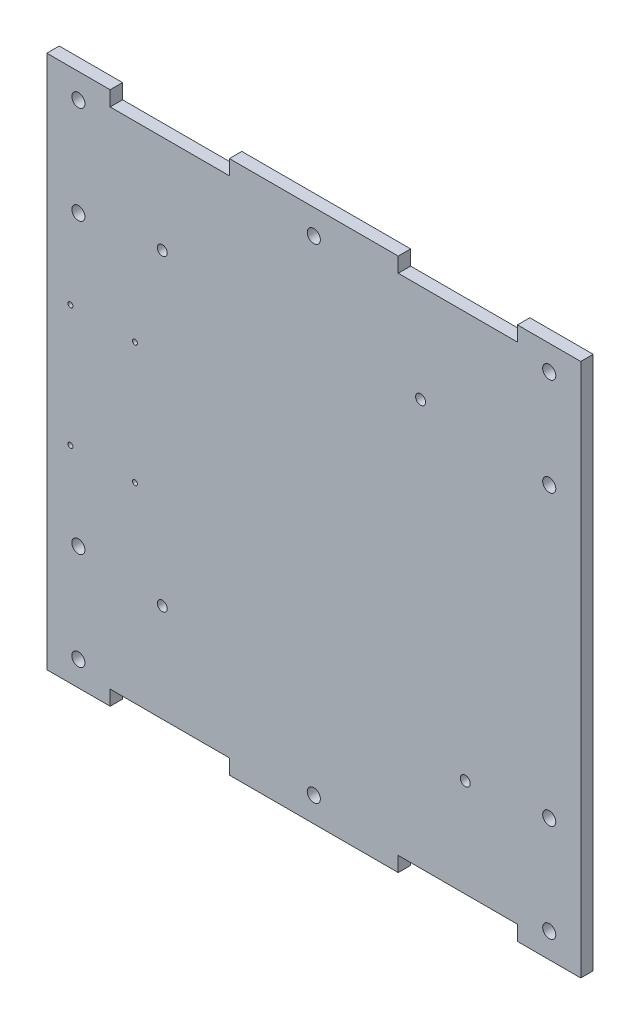
SolidWorks part; units mm, degrees
material "ABS PC"
ref_plane "Front Plane" through (0, 0, 0) normal (0, 0, 1) x (1, 0, 0)
ref_plane "Top Plane" through (0, 0, 0) normal (0, 1, 0) x (1, 0, 0)
ref_plane "Right Plane" through (0, 0, 0) normal (1, 0, 0) x (0, 0, -1)
sketch "Sketch2" plane through (0, 0, 0) normal (0, 0, 1) x (1, 0, 0)
  line L0 (-148.1492, 0) -> (167.2874, 0) construction
  line L1 (-136.525, -136.525) -> (136.525, -136.525)
  line L2 (-136.525, -136.525) -> (-136.525, 136.525)
  line L3 (-136.525, 136.525) -> (136.525, 136.525)
  line L4 (136.525, -136.525) -> (136.525, 136.525)
  line L5 (-136.525, -136.525) -> (136.525, 136.525) construction
  line L6 (-136.525, 136.525) -> (136.525, -136.525) construction
  line L7 (0, 204.6077) -> (0, -224.7364) construction
  circle A0 centre (-120.396, 123.825) radius 3.35
  circle A1 centre (-120.396, 73.787) radius 3.35
  circle A2 centre (0, 123.825) radius 3.35
  circle A3 centre (120.396, 73.787) radius 3.35
  circle A4 centre (120.396, 123.825) radius 3.35
  circle A5 centre (120.396, -123.825) radius 3.35
  circle A6 centre (120.396, -73.787) radius 3.35
  circle A7 centre (0, -123.825) radius 3.35
  circle A8 centre (-120.396, -73.787) radius 3.35
  circle A9 centre (-120.396, -123.825) radius 3.35
  point P0 (0, 0)
  dimension "D4" = 6.7
  dimension "D7" = 6.7
  dimension "D8" = 6.7
  dimension "D1" = 273.05
  dimension "D2" = 273.05
  dimension "D3" = 120.396
  dimension "D5" = 123.825
  dimension "D6" = 50.038
extrude "Boss-Extrude1" add sketch "Sketch2" along normal blind 6.35
sketch "Sketch3" plane through (0, 0, 6.35) normal (0, 0, 1) x (1, 0, 0)
  line L0 (0, 160.7885) -> (0, -171.3941) construction
  line L1 (-158.7053, 0) -> (205.6729, 0) construction
  line L4 (136.525, 136.525) -> (-136.525, 136.525) construction
  line L5 (104.14, 128.905) -> (43.18, 128.905)
  line L6 (104.14, 146.1851) -> (43.18, 146.1851)
  line L7 (-104.14, 146.1851) -> (-104.14, 128.905)
  line L8 (43.18, 128.905) -> (43.18, 146.1851)
  line L9 (104.14, 146.1851) -> (104.14, 128.905)
  line L10 (-104.14, -128.905) -> (-43.18, -128.905)
  line L11 (-43.18, 128.905) -> (-43.18, 146.1851)
  line L12 (-104.14, -146.1851) -> (-43.18, -146.1851)
  line L13 (-104.14, 146.1851) -> (-43.18, 146.1851)
  line L14 (-104.14, 128.905) -> (-43.18, 128.905)
  line L15 (-43.18, -128.905) -> (-43.18, -146.1851)
  line L16 (104.14, -146.1851) -> (104.14, -128.905)
  line L17 (43.18, -128.905) -> (43.18, -146.1851)
  line L18 (-104.14, -146.1851) -> (-104.14, -128.905)
  line L19 (104.14, -146.1851) -> (43.18, -146.1851)
  line L20 (104.14, -128.905) -> (43.18, -128.905)
  dimension "D1" = 7.62
  dimension "D2" = 43.18
  dimension "D3" = 104.14
extrude "Cut-Extrude1" cut sketch "Sketch3" against normal through all
sketch "Sketch4" plane through (0, 0, 6.35) normal (0, 0, 1) x (1, 0, 0)
  line L0 (0, 106.7981) -> (0, -152.8318) construction
  line L1 (-149.4258, 0) -> (166.1811, 0) construction
  circle A0 centre (-77.47, 78.74) radius 2.54
  circle A1 centre (-77.47, -78.74) radius 2.54
  circle A2 centre (77.47, -78.74) radius 2.54
  circle A3 centre (54.61, 78.74) radius 2.54
  dimension "D4" = 5.08
  dimension "D5" = 5.08
  dimension "D1" = 77.47
  dimension "D2" = 78.74
  dimension "D3" = 54.61
extrude "ITX_mounting_Holes" cut sketch "Sketch4" against normal through all
sketch "Sketch5" plane through (0, 0, 6.35) normal (0, 0, 1) x (1, 0, 0)
  line L0 (-146.8479, 0) -> (158.0792, 0) construction
  line L2 (-124.46, 31.115) -> (-91.44, 31.115) construction
  line L3 (-124.46, 31.115) -> (-124.46, -31.115) construction
  line L4 (-124.46, -31.115) -> (-91.44, -31.115) construction
  line L5 (-91.44, 31.115) -> (-91.44, -31.115) construction
  line L6 (-124.46, 31.115) -> (-91.44, -31.115) construction
  line L7 (-124.46, -31.115) -> (-91.44, 31.115) construction
  circle A0 centre (-124.46, 31.115) radius 1.27
  circle A1 centre (-91.44, 31.115) radius 1.27
  circle A2 centre (-91.44, -31.115) radius 1.27
  circle A3 centre (-124.46, -31.115) radius 1.27
  point P3 (-107.95, 0)
  dimension "D4" = 2.54
  dimension "D5" = 2.54
  dimension "D6" = 2.54
  dimension "D7" = 2.54
  dimension "D1" = 62.23
  dimension "D2" = 33.02
  dimension "D3" = 107.95
extrude "Cut-Extrude2" cut sketch "Sketch5" against normal through all
equation "\"D3@Sketch4\" = 5.2 -\"D1@Sketch4\""
